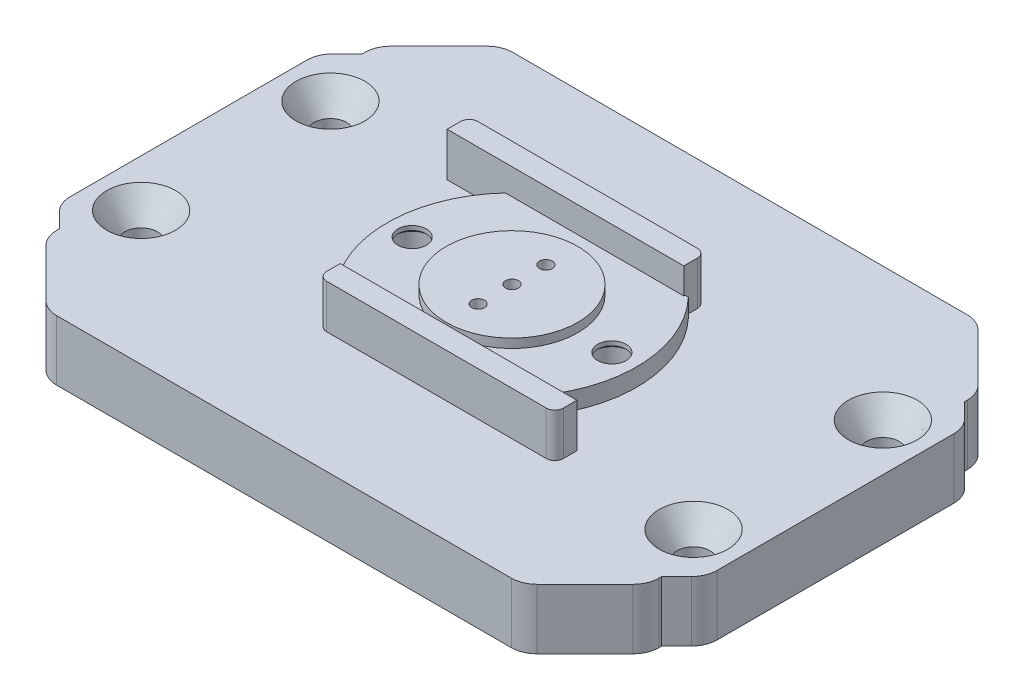
SolidWorks part; units mm, degrees
ref_plane "Front Plane" through (0, 0, 0) normal (0, 0, 1) x (1, 0, 0)
ref_plane "Top Plane" through (0, 0, 0) normal (0, 1, 0) x (1, 0, 0)
ref_plane "Right Plane" through (0, 0, 0) normal (1, 0, 0) x (0, 0, -1)
sketch "Sketch1" plane through (0, 0, 0) normal (0, 1, 0) x (1, 0, 0)
  line L0 (0, 26.5) -> (0, -26.5) construction
  line L1 (-35, 26.5) -> (35, 26.5)
  line L2 (-35, 26.5) -> (-35, -26.5)
  line L3 (-35, -26.5) -> (35, -26.5)
  line L4 (35, 26.5) -> (35, -26.5)
  line L5 (-35, 26.5) -> (35, -26.5) construction
  line L6 (-35, -26.5) -> (35, 26.5) construction
  line L7 (-11.608, 0) -> (11.608, 0) construction
  line L8 (-35, 0) -> (35, 0) construction
  line L10 (-28.7481, -10) -> (28.7481, -10)
  line L11 (-28.7481, -10) -> (-28.7481, 10)
  line L12 (-28.7481, 10) -> (28.7481, 10)
  line L13 (28.7481, -10) -> (28.7481, 10)
  line L14 (-28.7481, -10) -> (28.7481, 10) construction
  line L15 (-28.7481, 10) -> (28.7481, -10) construction
  circle A0 centre (0, 0) radius 14.5
  circle A1 centre (0, 0) radius 9.155
  circle A2 centre (0, 3.937) radius 0.75
  circle A3 centre (0, -3.937) radius 0.75
  circle A4 centre (0, 0) radius 0.75
  circle A5 centre (0, 0) radius 7.65
  circle A6 centre (-11.608, 0) radius 2.1
  circle A7 centre (11.608, 0) radius 2.1
  point P0 (0, 0)
  point P23 (0, 0)
  dimension "D3" = 15.3
  dimension "D4" = 18.31
  dimension "D5" = 1.5
  dimension "D6" = 29
  dimension "D8" = 4.2
  dimension "D1" = 53
  dimension "D2" = 70
  dimension "D7" = 7.874
  dimension "D9" = 23.216
  dimension "D10" = 20
extrude "Boss-Extrude1" add sketch "Sketch1" along normal blind 3.103 contours A5 A2 A3 A4 region at (-7.4336, 0, 0)
extrude "Boss-Extrude2" add sketch "Sketch1<3>" along normal blind 2.06 contours A1 A5 | A0 A7 A6 A1 region at (-14.1477, 0, 0) region at (-8.8961, 0, 0)
sketch "Sketch1<3>" plane through (0, 0, 0) normal (0, 1, 0) x (1, 0, 0) same geometry as "Sketch1"
sketch "Sketch2" plane through (0, 0, 0) normal (0, -1, 0) x (1, 0, 0)
  line L0 (0, -9.866) -> (0, 9.866) construction
  line L1 (17.4091, 12.432) -> (-10.0999, 12.432)
  line L2 (17.4091, 12.432) -> (17.4091, 9.866)
  line L3 (17.4091, 9.866) -> (-10.0999, 9.866)
  line L4 (-10.0999, 12.432) -> (-10.0999, 9.866)
  line L5 (-17.4091, -12.432) -> (10.0999, -12.432)
  line L6 (-17.4091, -12.432) -> (-17.4091, -9.866)
  line L7 (-17.4091, -9.866) -> (10.0999, -9.866)
  line L8 (10.0999, -12.432) -> (10.0999, -9.866)
  line L9 (-13.708, 0) -> (14.5, 0) construction
  circle A0 centre (-11.608, 0) radius 2.1 construction
  circle A1 centre (0, 0) radius 14.5 construction
  dimension "D1" = 2.566
  dimension "D2" = 27.509
  dimension "D3" = 19.732
  dimension "D4" = 28.238
extrude "Boss-Extrude3" add sketch "Sketch2" against normal blind 5.084 contours L7 L8 L5 L6 | L4 L3 L2 L1
sketch "Sketch3" plane through (0, 0, 0) normal (0, -1, 0) x (1, 0, 0)
  line L0 (31, -17.5) -> (31, -14.8458)
  line L5 (26, -22.5) -> (31, -17.5)
  line L6 (-26, -22.5) -> (26, -22.5)
  line L7 (-31, -17.5) -> (-26, -22.5)
  line L8 (-31, -14.8458) -> (-31, -17.5)
  line L9 (-31, 7.1542) -> (-31, -7.1542)
  line L10 (-31, 17.5) -> (-31, 14.8458)
  line L11 (-26, 22.5) -> (-31, 17.5)
  line L12 (26, 22.5) -> (-26, 22.5)
  line L13 (31, 17.5) -> (26, 22.5)
  line L14 (31, 14.8458) -> (31, 17.5)
  line L15 (31, -7.1542) -> (31, 7.1542)
  line L16 (-17.4091, -9.866) -> (-17.4091, -12.432)
  line L17 (-17.4091, -12.432) -> (10.0999, -12.432)
  line L18 (10.0999, -12.432) -> (10.0999, -10)
  line L19 (-10.626, -9.866) -> (-17.4091, -9.866)
  line L20 (10.626, 9.866) -> (17.4091, 9.866)
  line L21 (17.4091, 9.866) -> (17.4091, 12.432)
  line L22 (17.4091, 12.432) -> (-10.0999, 12.432)
  line L23 (-10.0999, 12.432) -> (-10.0999, 10)
  line L24 (10.0999, -10) -> (10.5, -10)
  line L25 (10.0999, -10) -> (10.5, -10)
  line L26 (-17.4091, -9.866) -> (-17.4091, -12.432)
  line L27 (-17.4091, -12.432) -> (10.0999, -12.432)
  line L28 (10.0999, -12.432) -> (10.0999, -10)
  line L29 (-10.626, -9.866) -> (-17.4091, -9.866)
  line L30 (10.626, 9.866) -> (17.4091, 9.866)
  line L31 (17.4091, 9.866) -> (17.4091, 12.432)
  line L32 (17.4091, 12.432) -> (-10.0999, 12.432)
  line L33 (-10.0999, 12.432) -> (-10.0999, 10)
  line L36 (37.6, -13.7574) -> (37.6, 13.7574)
  line L37 (36.7213, 15.8787) -> (35, 17.6)
  line L38 (35, 17.6) -> (35, 17.9142)
  line L39 (34.1213, 20.0355) -> (28.5355, 25.6213)
  line L40 (26.4142, 26.5) -> (-26.4142, 26.5)
  line L41 (-28.5355, 25.6213) -> (-34.1213, 20.0355)
  line L42 (-35, 17.9142) -> (-35, 17.6)
  line L43 (-35, 17.6) -> (-36.7213, 15.8787)
  line L44 (-37.6, 13.7574) -> (-37.6, -13.7574)
  line L45 (-36.7213, -15.8787) -> (-35, -17.6)
  line L46 (-35, -17.6) -> (-35, -17.9142)
  line L47 (-34.1213, -20.0355) -> (-28.5355, -25.6213)
  line L48 (-26.4142, -26.5) -> (26.4142, -26.5)
  line L49 (28.5355, -25.6213) -> (34.1213, -20.0355)
  line L50 (35, -17.9142) -> (35, -17.6)
  line L51 (35, -17.6) -> (36.7213, -15.8787)
  line L52 (-37.6, 0) -> (37.6, 0) construction
  line L54 (0, 26.5) -> (0, -26.5) construction
  line L64 (-10.0999, 10) -> (-10.5, 10)
  line L65 (-10.0999, 10) -> (-10.5, 10)
  circle A0 centre (0, 0) radius 6.404
  circle A1 centre (0, -3.937) radius 0.75
  circle A2 centre (0, -3.937) radius 0.75
  circle A3 centre (0, 3.937) radius 0.75
  circle A4 centre (0, 3.937) radius 0.75
  circle A5 centre (0, 0) radius 0.75
  arc A8 (10.5, -10) -> (10.626, 9.866) centre (0, 0) ccw
  arc A11 (-10.5, 10) -> (-10.626, -9.866) centre (0, 0) ccw
  arc A14 (10.5, -10) -> (10.626, 9.866) centre (0, 0) ccw
  arc A17 (-10.5, 10) -> (-10.626, -9.866) centre (0, 0) ccw
  circle A18 centre (0, 0) radius 0.75
  circle A19 centre (11.608, 0) radius 2.1
  circle A20 centre (11.608, 0) radius 2.1
  circle A21 centre (-11.608, 0) radius 2.1
  circle A22 centre (-11.608, 0) radius 2.1
  circle A23 centre (-32.1, -11) radius 1.9
  arc A24 (31, -7.1542) -> (31, -14.8458) centre (32.1, -11) ccw
  arc A25 (-31, -14.8458) -> (-31, -7.1542) centre (-32.1, -11) ccw
  arc A26 (-31, 7.1542) -> (-31, 14.8458) centre (-32.1, 11) ccw
  arc A27 (31, 14.8458) -> (31, 7.1542) centre (32.1, 11) ccw
  circle A28 centre (-32.1, 11) radius 1.9
  circle A29 centre (32.1, 11) radius 1.9
  circle A30 centre (32.1, -11) radius 1.9
  arc A31 (37.6, 13.7574) -> (36.7213, 15.8787) centre (34.6, 13.7574) ccw
  arc A32 (35, 17.9142) -> (34.1213, 20.0355) centre (32, 17.9142) ccw
  arc A33 (28.5355, 25.6213) -> (26.4142, 26.5) centre (26.4142, 23.5) ccw
  arc A34 (-26.4142, 26.5) -> (-28.5355, 25.6213) centre (-26.4142, 23.5) ccw
  arc A35 (-34.1213, 20.0355) -> (-35, 17.9142) centre (-32, 17.9142) ccw
  arc A36 (-36.7213, 15.8787) -> (-37.6, 13.7574) centre (-34.6, 13.7574) ccw
  arc A37 (-37.6, -13.7574) -> (-36.7213, -15.8787) centre (-34.6, -13.7574) ccw
  arc A38 (-35, -17.9142) -> (-34.1213, -20.0355) centre (-32, -17.9142) ccw
  arc A39 (-28.5355, -25.6213) -> (-26.4142, -26.5) centre (-26.4142, -23.5) ccw
  arc A40 (26.4142, -26.5) -> (28.5355, -25.6213) centre (26.4142, -23.5) ccw
  arc A41 (34.1213, -20.0355) -> (35, -17.9142) centre (32, -17.9142) ccw
  arc A42 (36.7213, -15.8787) -> (37.6, -13.7574) centre (34.6, -13.7574) ccw
  point P0 (0, 0)
  line M3 (-17.4091, -9.866) -> (-17.4091, -12.432)
  line M5 (-17.4091, -12.432) -> (10.0999, -12.432)
  line M7 (10.0999, -12.432) -> (10.0999, -10)
  arc M9 (10.5, -10) -> (10.626, 9.866) centre (0, 0) ccw
  line M10 (10.626, 9.866) -> (17.4091, 9.866)
  line M11 (17.4091, 9.866) -> (17.4091, 12.432)
  line M13 (17.4091, 12.432) -> (-10.0999, 12.432)
  line M15 (-10.0999, 12.432) -> (-10.0999, 10)
  arc M17 (-10.5, 10) -> (-10.626, -9.866) centre (0, 0) ccw
  line M18 (-10.626, -9.866) -> (-17.4091, -9.866)
  circle M19 centre (0, -3.937) radius 0.75
  circle M20 centre (0, 3.937) radius 0.75
  circle M21 centre (0, 0) radius 0.75
  circle M22 centre (11.608, 0) radius 2.1
  circle M23 centre (-11.608, 0) radius 2.1
  dimension "D9" = 12.808
  dimension "D3" = 0
  dimension "D4" = 0
  dimension "D5" = 0
  dimension "D6" = 0
  dimension "D7" = 0
  dimension "D8" = 0
extrude "Boss-Extrude4" add sketch "Sketch3" along normal blind 0.4 contours A27 L14 L13 L12 L11 L10 A26 L9 A25 L8 L7 L6 L5 L0 A24 L15 M3 M18 M17 M15 M13 M11 M10 M9 M7 M5 | A0 M18 M3 M5 M7 M9 M10 M11 M13 M15 M17 M23 M22 | A0 M20 M21 M19 | L51 A42 L36 A31 L37 L38 A32 L39 A33 L40 A34 L41 A35 L42 L43 A36 L44 A37 L45 L46 A38 L47 A39 L48 A40 L49 A41 L50 L14 A27 L15 A24 L0 L5 L6 L7 L8 A25 L9 A26 L10 L11 L12 L13 A23 A28 A29 region at (27.9583, 0, -19.4583) region at (-14.0175, 0, -10.2938) region at (36.5217, 0, -14.5533) region at (-6.2229, 0, 0)
extrude "Boss-Extrude5" add sketch "Sketch3<3>" along normal blind 3.6 contours M3 M18 M17 M15 M13 M11 M10 M9 M7 M5 | A0 M18 M3 M5 M7 M9 M10 M11 M13 M15 M17 M23 M22 | L51 A42 L36 A31 L37 L38 A32 L39 A33 L40 A34 L41 A35 L42 L43 A36 L44 A37 L45 L46 A38 L47 A39 L48 A40 L49 A41 L50 L14 A27 L15 A24 L0 L5 L6 L7 L8 A25 L9 A26 L10 L11 L12 L13 A23 A28 A29 region at (27.9583, 0, -19.4583) region at (-14.0175, 0, -10.2938) region at (36.5217, 0, -14.5533)
sketch "Sketch3<3>" plane through (0, 0, 0) normal (0, -1, 0) x (1, 0, 0) same geometry as "Sketch3"
extrude "Boss-Extrude6" add sketch "Sketch3<4>" along normal blind 7 contours L51 A42 L36 A31 L37 L38 A32 L39 A33 L40 A34 L41 A35 L42 L43 A36 L44 A37 L45 L46 A38 L47 A39 L48 A40 L49 A41 L50 L14 A27 L15 A24 L0 L5 L6 L7 L8 A25 L9 A26 L10 L11 L12 L13 A23 A28 A29 region at (36.5217, 0, -14.5533)
sketch "Sketch3<4>" plane through (0, 0, 0) normal (0, -1, 0) x (1, 0, 0) same geometry as "Sketch3"
fillet "Fillet1" radius 1 4 edges at (-17.4091, 2.542, -12.432) (10.0999, 2.542, -12.432) (17.4091, 2.542, 12.432) (-10.0999, 2.542, 12.432)
chamfer "Chamfer1" distance 3.1 distance2 2.1 4 edges at (32.1, 0, -12.9) (32.1, 0, 9.1) (-32.1, 0, 9.1) (-32.1, 0, -12.9) first distance on face at (32.1, 0, -12.9) first distance on face at (32.1, 0, 9.1) first distance on face at (-32.1, 0, 9.1) first distance on face at (-32.1, 0, -12.9)
sketch "Sketch4" plane through (0, -0.4, 0) normal (0, -1, 0) x (1, 0, 0)
  circle A0 centre (0, 3.937) radius 1
  circle A1 centre (0, 3.937) radius 0.75
  circle A2 centre (0, 3.937) radius 0.75
  circle A3 centre (0, 0) radius 0.75
  circle A4 centre (0, 0) radius 0.75
  circle A5 centre (0, -3.937) radius 0.75
  circle A6 centre (0, -3.937) radius 0.75
  circle A7 centre (0, 0) radius 6.404
  circle A8 centre (0, 0) radius 6.404
  circle A9 centre (0, 0) radius 1
  circle A10 centre (0, -3.937) radius 1
  circle M5 centre (0, 0) radius 6.404
  dimension "D5" = 2
  dimension "D1" = 0
  dimension "D2" = 0
  dimension "D3" = 0
  dimension "D4" = 0
extrude "Boss-Extrude7" add sketch "Sketch4" along normal blind 0.5 contours A10 A9 A0 M5 region at (-6.2229, -0.4, 0)
sketch "Sketch5" plane through (0, -0.9, 0) normal (0, -1, 0) x (1, 0, 0)
  line L0 (-1, 6.3254) -> (-1, -6.3254)
  line L2 (1, 6.3254) -> (1, -6.3254)
  circle A0 centre (0, 0) radius 6.404
  circle A1 centre (0, 0) radius 6.404 construction
  circle A2 centre (0, 0) radius 6.404 construction
  circle A3 centre (0, 0) radius 1 construction
  circle M6 centre (0, 0) radius 6.404
extrude "Boss-Extrude8" add sketch "Sketch5" along normal blind 0.3 contours L0 M6 | L2 M6 region at (-3.2658, -0.9, 0) region at (3.2658, -0.9, 0)
sketch "Sketch6" plane through (0, 2.06, 0) normal (0, 1, 0) x (1, 0, 0)
  circle A0 centre (-11.608, 0) radius 2.125
  circle A1 centre (11.608, 0) radius 2.125
  circle A2 centre (11.608, 0) radius 1.65
  circle A3 centre (-11.608, 0) radius 1.65
  dimension "D1" = 3.3
  dimension "D2" = 3.3
extrude "Boss-Extrude9" add sketch "Sketch6" against normal blind 0.5
chamfer "Chamfer2" distance 0.4 angle 45 2 edges at (-11.608, 1.56, 2.1) (11.608, 1.56, 2.1)
